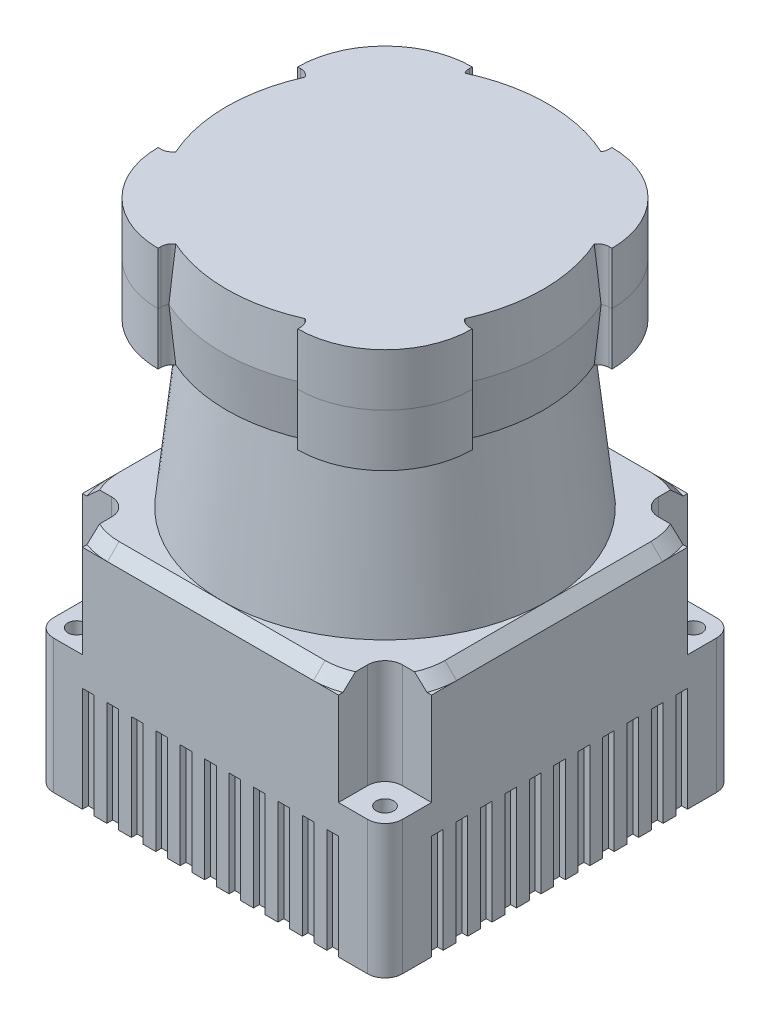
SolidWorks part; units mm, degrees
note: The reader was unsure of these and kept them because the rebuilt part matched: shared geometry of "Sketch11<3>".
ref_plane "Front Plane" through (0, 0, 0) normal (0, 0, 1) x (1, 0, 0)
ref_plane "Top Plane" through (0, 0, 0) normal (0, 1, 0) x (1, 0, 0)
ref_plane "Right Plane" through (0, 0, 0) normal (1, 0, 0) x (0, 0, -1)
sketch "Sketch2" plane through (0, 0, 0) normal (0, 0, 1) x (1, 0, 0)
  line L0 (0, 0) -> (-28, 0)
  line L1 (-28, 0) -> (-25, 28)
  line L2 (-25, 28) -> (0, 28)
  line L3 (0, 28) -> (0, 0)
  dimension "D1" = 28
  dimension "D2" = 25
  dimension "D3" = 28
revolve "Revolve1" add sketch "Sketch2" angle 360 about L3
sketch "Sketch3" plane through (0, 0, 0) normal (1, 0, 0) x (0, 0, -1)
  line L0 (25, 28) -> (-25, 28) construction
  line L1 (0, 28) -> (28, 28)
  line L2 (0, 28) -> (0, 0)
  line L3 (0, 0) -> (28, 0)
  line L4 (28, 28) -> (28, 0)
extrude "Boss-Extrude1" add sketch "Sketch3" along normal mid plane 10
sketch "Sketch4" plane through (0, 0, 0) normal (0, 1, 0) x (1, 0, 0)
  line L0 (-26.5, 30) -> (-26.5, 26.5) construction
  line L1 (27, -30) -> (-27, -30)
  line L2 (30, -27) -> (30, 27)
  line L3 (27, 30) -> (-27, 30)
  line L4 (-30, -27) -> (-30, 27)
  line L5 (30, -30) -> (-30, 30) construction
  line L6 (30, 30) -> (-30, -30) construction
  line L7 (-26.5, 26.5) -> (-30, 26.5) construction
  line L8 (26.5, 26.5) -> (26.5, 30) construction
  line L9 (30, 26.5) -> (26.5, 26.5) construction
  line L10 (26.5, -26.5) -> (30, -26.5) construction
  line L11 (26.5, -30) -> (26.5, -26.5) construction
  line L12 (-26.5, -26.5) -> (-26.5, -30) construction
  line L13 (-30, -26.5) -> (-26.5, -26.5) construction
  arc A0 (-27, -30) -> (-30, -27) centre (-27, -27) cw
  arc A1 (30, -27) -> (27, -30) centre (27, -27) cw
  arc A2 (30, 27) -> (27, 30) centre (27, 27) ccw
  arc A3 (-27, 30) -> (-30, 27) centre (-27, 27) ccw
  circle A4 centre (-26.5, 26.5) radius 1.5
  circle A5 centre (26.5, 26.5) radius 1.5
  circle A6 centre (26.5, -26.5) radius 1.5
  circle A7 centre (-26.5, -26.5) radius 1.5
  point P0 (0, 0)
  point P37 (0, 0)
  dimension "D2" = 3
  dimension "D4" = 3
  dimension "D1" = 60
  dimension "D3" = 3.5
  dimension "D5" = 4
extrude "Boss-Extrude2" add sketch "Sketch4" against normal blind 39 from offset 2 offset against normal yes
sketch "Sketch5" plane through (0, 0, 0) normal (0, 0, 1) x (1, 0, 0)
  line L0 (0, -2) -> (0, -41) construction
  line L1 (-27, -2) -> (27, -2) construction
  line L2 (-27, -41) -> (27, -41) construction
  circle A0 centre (-15, -32) radius 3.5
  circle A1 centre (15, -32) radius 3.5
  dimension "D3" = 7
  dimension "D1" = 9
  dimension "D2" = 15
extrude "Cut-Extrude1" cut sketch "Sketch5" along normal blind 5 from surface at -30 starting at face at (0, -21.5, -30)
sketch "Sketch7" plane through (0, -2, 0) normal (0, 1, 0) x (1, 0, 0)
  line L2 (27, 25) -> (-27, 25)
  line L3 (17.7, 25) -> (-17.7, 25)
  line L17 (-25, 27) -> (-25, -27)
  line L18 (-25, 17.7) -> (-25, -17.7)
  line L20 (-27, -25) -> (27, -25)
  line L21 (-17.7, -25) -> (17.7, -25)
  line L23 (25, -27) -> (25, 27)
  line L24 (25, -17.7) -> (25, 17.7)
  arc A0 (-17.7, 25) -> (-25, 17.7) centre (-17.7, 17.7) ccw
  arc A1 (-17.7, -25) -> (-25, -17.7) centre (-17.7, -17.7) cw
  arc A2 (25, -17.7) -> (17.7, -25) centre (17.7, -17.7) cw
  arc A3 (25, 17.7) -> (17.7, 25) centre (17.7, 17.7) ccw
  dimension "D5" = 7.3
  dimension "D6" = 7.3
  dimension "D1" = 5
  dimension "D2" = 5
  dimension "D3" = 5
  dimension "D4" = 5
sketch "Sketch9" plane through (0, 0, 0) normal (1, 0, 0) x (0, 0, -1)
  line L0 (-30, -2) -> (-28, 0)
  line L1 (-28, 0) -> (27.55, 0) construction
  line L2 (-28, 0) -> (-20, 0)
  line L3 (-20, 0) -> (-20, -2)
  line L4 (-27, -2) -> (27, -2) construction
  line L5 (-20, -2) -> (-30, -2)
  dimension "D1" = 10
sweep "Sweep2" add profiles "Sketch9" path "Sketch7"
sketch "Sketch6" plane through (0, 0, 0) normal (0, 1, 0) x (1, 0, 0)
  line L0 (-30, 22) -> (-25, 22)
  line L1 (-22, 25) -> (-22, 30)
  line L2 (27, 30) -> (17.7, 30) construction
  line L3 (-30, 27) -> (-30, 17.7) construction
  line L4 (-17.7, 30) -> (-27, 30) construction
  line L5 (-30, 27) -> (-30, 22)
  line L6 (30, 22) -> (30, 27)
  line L7 (25, 22) -> (30, 22)
  line L8 (22, 30) -> (22, 25)
  line L9 (27, 30) -> (22, 30)
  line L10 (22, -30) -> (27, -30)
  line L11 (22, -25) -> (22, -30)
  line L12 (30, -22) -> (25, -22)
  line L13 (30, -27) -> (30, -22)
  line L14 (-30, -22) -> (-30, -27)
  line L15 (-25, -22) -> (-30, -22)
  line L16 (-22, -30) -> (-22, -25)
  line L17 (-27, -30) -> (-22, -30)
  line L18 (-22, 30) -> (-27, 30)
  arc A0 (-22, 25) -> (-25, 22) centre (-25, 25) cw
  arc A2 (-27, 30) -> (-30, 27) centre (-27, 27) ccw construction
  arc A3 (30, 27) -> (27, 30) centre (27, 27) ccw
  arc A4 (25, 22) -> (22, 25) centre (25, 25) cw
  arc A5 (27, -30) -> (30, -27) centre (27, -27) ccw
  arc A6 (22, -25) -> (25, -22) centre (25, -25) cw
  arc A7 (-30, -27) -> (-27, -30) centre (-27, -27) ccw
  arc A8 (-25, -22) -> (-22, -25) centre (-25, -25) cw
  arc A9 (-27, 30) -> (-30, 27) centre (-27, 27) ccw
  point P9 (-22, 22)
  point P38 (0, 0)
  dimension "D2" = 3
  dimension "D1" = 8
  dimension "D3" = 4
extrude "Cut-Extrude2" cut sketch "Sketch6" against normal blind 18
sketch "Sketch10" plane through (0, -41, 0) normal (0, -1, 0) x (1, 0, 0)
  line L0 (-30, 0) -> (30, 0) construction
  line L1 (-30, -27) -> (-30, 27) construction
  line L2 (30, 27) -> (30, -27) construction
  line L3 (0, 30) -> (0, -30) construction
  line L4 (-27, 30) -> (27, 30) construction
  line L5 (27, -30) -> (-27, -30) construction
  line L6 (-30, 17.8) -> (-30, 15.8)
  line L7 (-30, 22) -> (-29, 22)
  line L8 (-30, 22) -> (-30, 20)
  line L9 (-30, 20) -> (-29, 20)
  line L10 (-29, 22) -> (-29, 20)
  line L11 (-30, 15.8) -> (-29, 15.8)
  line L12 (-29, 17.8) -> (-29, 15.8)
  line L13 (-30, 17.8) -> (-29, 17.8)
  line L14 (-30, 13.6) -> (-30, 11.6)
  line L15 (-30, 11.6) -> (-29, 11.6)
  line L16 (-29, 13.6) -> (-29, 11.6)
  line L17 (-30, 13.6) -> (-29, 13.6)
  line L18 (-30, 9.4) -> (-30, 7.4)
  line L19 (-30, 7.4) -> (-29, 7.4)
  line L20 (-29, 9.4) -> (-29, 7.4)
  line L21 (-30, 9.4) -> (-29, 9.4)
  line L22 (-30, 5.2) -> (-30, 3.2)
  line L23 (-30, 3.2) -> (-29, 3.2)
  line L24 (-29, 5.2) -> (-29, 3.2)
  line L25 (-30, 5.2) -> (-29, 5.2)
  line L26 (-30, 1) -> (-30, -1)
  line L27 (-30, -1) -> (-29, -1)
  line L28 (-29, 1) -> (-29, -1)
  line L29 (-30, 1) -> (-29, 1)
  line L30 (-30, -3.2) -> (-30, -5.2)
  line L31 (-30, -5.2) -> (-29, -5.2)
  line L32 (-29, -3.2) -> (-29, -5.2)
  line L33 (-30, -3.2) -> (-29, -3.2)
  line L34 (-30, -7.4) -> (-30, -9.4)
  line L35 (-30, -9.4) -> (-29, -9.4)
  line L36 (-29, -7.4) -> (-29, -9.4)
  line L37 (-30, -7.4) -> (-29, -7.4)
  line L38 (-30, -11.6) -> (-30, -13.6)
  line L39 (-30, -13.6) -> (-29, -13.6)
  line L40 (-29, -11.6) -> (-29, -13.6)
  line L41 (-30, -11.6) -> (-29, -11.6)
  line L42 (-30, -15.8) -> (-30, -17.8)
  line L43 (-30, -17.8) -> (-29, -17.8)
  line L44 (-29, -15.8) -> (-29, -17.8)
  line L45 (-30, -15.8) -> (-29, -15.8)
  line L46 (-30, -20) -> (-30, -22)
  line L47 (-30, -22) -> (-29, -22)
  line L48 (-29, -20) -> (-29, -22)
  line L49 (-30, -20) -> (-29, -20)
  line L50 (17.8, 30) -> (15.8, 30)
  line L51 (22, 30) -> (22, 29)
  line L52 (22, 30) -> (20, 30)
  line L53 (20, 30) -> (20, 29)
  line L54 (22, 29) -> (20, 29)
  line L55 (15.8, 30) -> (15.8, 29)
  line L56 (17.8, 29) -> (15.8, 29)
  line L57 (17.8, 30) -> (17.8, 29)
  line L58 (13.6, 30) -> (11.6, 30)
  line L59 (11.6, 30) -> (11.6, 29)
  line L60 (13.6, 29) -> (11.6, 29)
  line L61 (13.6, 30) -> (13.6, 29)
  line L62 (9.4, 30) -> (7.4, 30)
  line L63 (7.4, 30) -> (7.4, 29)
  line L64 (9.4, 29) -> (7.4, 29)
  line L65 (9.4, 30) -> (9.4, 29)
  line L66 (5.2, 30) -> (3.2, 30)
  line L67 (3.2, 30) -> (3.2, 29)
  line L68 (5.2, 29) -> (3.2, 29)
  line L69 (5.2, 30) -> (5.2, 29)
  line L70 (1, 30) -> (-1, 30)
  line L71 (-1, 30) -> (-1, 29)
  line L72 (1, 29) -> (-1, 29)
  line L73 (1, 30) -> (1, 29)
  line L74 (-3.2, 30) -> (-5.2, 30)
  line L75 (-5.2, 30) -> (-5.2, 29)
  line L76 (-3.2, 29) -> (-5.2, 29)
  line L77 (-3.2, 30) -> (-3.2, 29)
  line L78 (-7.4, 30) -> (-9.4, 30)
  line L79 (-9.4, 30) -> (-9.4, 29)
  line L80 (-7.4, 29) -> (-9.4, 29)
  line L81 (-7.4, 30) -> (-7.4, 29)
  line L82 (-11.6, 30) -> (-13.6, 30)
  line L83 (-13.6, 30) -> (-13.6, 29)
  line L84 (-11.6, 29) -> (-13.6, 29)
  line L85 (-11.6, 30) -> (-11.6, 29)
  line L86 (-15.8, 30) -> (-17.8, 30)
  line L87 (-17.8, 30) -> (-17.8, 29)
  line L88 (-15.8, 29) -> (-17.8, 29)
  line L89 (-15.8, 30) -> (-15.8, 29)
  line L90 (-20, 30) -> (-22, 30)
  line L91 (-22, 30) -> (-22, 29)
  line L92 (-20, 29) -> (-22, 29)
  line L93 (-20, 30) -> (-20, 29)
  line L94 (30, -17.8) -> (30, -15.8)
  line L95 (30, -22) -> (29, -22)
  line L96 (30, -22) -> (30, -20)
  line L97 (30, -20) -> (29, -20)
  line L98 (29, -22) -> (29, -20)
  line L99 (30, -15.8) -> (29, -15.8)
  line L100 (29, -17.8) -> (29, -15.8)
  line L101 (30, -17.8) -> (29, -17.8)
  line L102 (30, -13.6) -> (30, -11.6)
  line L103 (30, -11.6) -> (29, -11.6)
  line L104 (29, -13.6) -> (29, -11.6)
  line L105 (30, -13.6) -> (29, -13.6)
  line L106 (30, -9.4) -> (30, -7.4)
  line L107 (30, -7.4) -> (29, -7.4)
  line L108 (29, -9.4) -> (29, -7.4)
  line L109 (30, -9.4) -> (29, -9.4)
  line L110 (30, -5.2) -> (30, -3.2)
  line L111 (30, -3.2) -> (29, -3.2)
  line L112 (29, -5.2) -> (29, -3.2)
  line L113 (30, -5.2) -> (29, -5.2)
  line L114 (30, -1) -> (30, 1)
  line L115 (30, 1) -> (29, 1)
  line L116 (29, -1) -> (29, 1)
  line L117 (30, -1) -> (29, -1)
  line L118 (30, 3.2) -> (30, 5.2)
  line L119 (30, 5.2) -> (29, 5.2)
  line L120 (29, 3.2) -> (29, 5.2)
  line L121 (30, 3.2) -> (29, 3.2)
  line L122 (30, 7.4) -> (30, 9.4)
  line L123 (30, 9.4) -> (29, 9.4)
  line L124 (29, 7.4) -> (29, 9.4)
  line L125 (30, 7.4) -> (29, 7.4)
  line L126 (30, 11.6) -> (30, 13.6)
  line L127 (30, 13.6) -> (29, 13.6)
  line L128 (29, 11.6) -> (29, 13.6)
  line L129 (30, 11.6) -> (29, 11.6)
  line L130 (30, 15.8) -> (30, 17.8)
  line L131 (30, 17.8) -> (29, 17.8)
  line L132 (29, 15.8) -> (29, 17.8)
  line L133 (30, 15.8) -> (29, 15.8)
  line L134 (30, 20) -> (30, 22)
  line L135 (30, 22) -> (29, 22)
  line L136 (29, 20) -> (29, 22)
  line L137 (30, 20) -> (29, 20)
  line L138 (-17.8, -30) -> (-15.8, -30)
  line L139 (-22, -30) -> (-22, -29)
  line L140 (-22, -30) -> (-20, -30)
  line L141 (-20, -30) -> (-20, -29)
  line L142 (-22, -29) -> (-20, -29)
  line L143 (-15.8, -30) -> (-15.8, -29)
  line L144 (-17.8, -29) -> (-15.8, -29)
  line L145 (-17.8, -30) -> (-17.8, -29)
  line L146 (-13.6, -30) -> (-11.6, -30)
  line L147 (-11.6, -30) -> (-11.6, -29)
  line L148 (-13.6, -29) -> (-11.6, -29)
  line L149 (-13.6, -30) -> (-13.6, -29)
  line L150 (-9.4, -30) -> (-7.4, -30)
  line L151 (-7.4, -30) -> (-7.4, -29)
  line L152 (-9.4, -29) -> (-7.4, -29)
  line L153 (-9.4, -30) -> (-9.4, -29)
  line L154 (-5.2, -30) -> (-3.2, -30)
  line L155 (-3.2, -30) -> (-3.2, -29)
  line L156 (-5.2, -29) -> (-3.2, -29)
  line L157 (-5.2, -30) -> (-5.2, -29)
  line L158 (-1, -30) -> (1, -30)
  line L159 (1, -30) -> (1, -29)
  line L160 (-1, -29) -> (1, -29)
  line L161 (-1, -30) -> (-1, -29)
  line L162 (3.2, -30) -> (5.2, -30)
  line L163 (5.2, -30) -> (5.2, -29)
  line L164 (3.2, -29) -> (5.2, -29)
  line L165 (3.2, -30) -> (3.2, -29)
  line L166 (7.4, -30) -> (9.4, -30)
  line L167 (9.4, -30) -> (9.4, -29)
  line L168 (7.4, -29) -> (9.4, -29)
  line L169 (7.4, -30) -> (7.4, -29)
  line L170 (11.6, -30) -> (13.6, -30)
  line L171 (13.6, -30) -> (13.6, -29)
  line L172 (11.6, -29) -> (13.6, -29)
  line L173 (11.6, -30) -> (11.6, -29)
  line L174 (15.8, -30) -> (17.8, -30)
  line L175 (17.8, -30) -> (17.8, -29)
  line L176 (15.8, -29) -> (17.8, -29)
  line L177 (15.8, -30) -> (15.8, -29)
  line L178 (20, -30) -> (22, -30)
  line L179 (22, -30) -> (22, -29)
  line L180 (20, -29) -> (22, -29)
  line L181 (20, -30) -> (20, -29)
  point P192 (0, 0)
  dimension "D1" = 1
  dimension "D2" = 2
  dimension "D3" = 8
  dimension "D5" = 4
  dimension "D4" = 11
extrude "Cut-Extrude3" cut sketch "Sketch10" against normal blind 18
ref_plane "Plane1" through (0, 37, 0) normal (0, 1, 0) x (1, 0, 0)
sketch "Sketch11" plane through (0, 37, 0) normal (0, 1, 0) x (1, 0, 0)
  line L0 (-10, 24.5) -> (10, 24.5)
  line L1 (27, -27) -> (-27, -27) construction
  line L2 (27, -27) -> (27, 27) construction
  line L3 (27, 27) -> (-27, 27) construction
  line L4 (-27, -27) -> (-27, 7.2357) construction
  line L5 (27, -27) -> (-27, 27) construction
  line L6 (27, 27) -> (-27, -27) construction
  line L7 (0, 28) -> (0, 24.5) construction
  line L8 (-12, 26.5) -> (-12, 27)
  line L9 (12, 26.5) -> (12, 27)
  line L10 (26.5, 12) -> (27, 12)
  line L11 (24.5, 10) -> (24.5, -10)
  line L12 (26.5, -12) -> (27, -12)
  line L13 (12, -26.5) -> (12, -27)
  line L14 (10, -24.5) -> (-10, -24.5)
  line L15 (-12, -26.5) -> (-12, -27)
  line L16 (-26.5, -12) -> (-27, -12)
  line L17 (-24.5, -10) -> (-24.5, 10)
  line L18 (-26.5, 12) -> (-27, 12)
  circle A0 centre (0, 0) radius 28
  arc A1 (-12, 27) -> (-27, 12) centre (-12, 12) ccw
  arc A2 (26.5, 12) -> (24.5, 10) centre (26.5, 10) ccw
  arc A3 (-27, -12) -> (-12, -27) centre (-12, -12) ccw
  arc A4 (12, 26.5) -> (10, 24.5) centre (10, 26.5) cw
  arc A5 (26.5, -12) -> (24.5, -10) centre (26.5, -10) cw
  arc A7 (12, -27) -> (27, -12) centre (12, -12) ccw
  arc A8 (-12, 26.5) -> (-10, 24.5) centre (-10, 26.5) ccw
  arc A9 (12, -26.5) -> (10, -24.5) centre (10, -26.5) ccw
  arc A10 (-12, -26.5) -> (-10, -24.5) centre (-10, -26.5) cw
  arc A11 (-26.5, -12) -> (-24.5, -10) centre (-26.5, -10) ccw
  arc A12 (-26.5, 12) -> (-24.5, 10) centre (-26.5, 10) cw
  arc A13 (27, 12) -> (12, 27) centre (12, 12) ccw
  point P0 (0, 0)
  point P20 (0, 24.5)
  point P27 (12, 24.5)
  point P30 (-12, 24.5)
  point P55 (0, 0)
  dimension "D2" = 56
  dimension "D4" = 24
  dimension "D6" = 2
  dimension "D1" = 54
  dimension "D5" = 3.5
extrude "Boss-Extrude3" add sketch "Sketch11" along normal mid plane 18 draft 5
extrude "Boss-Extrude4" add sketch "Sketch11<3>" along normal mid plane 18 contours L18 A12 A0 A8 L8 A1 | A0 A12 L17 A11 A10 L14 A9 A5 L11 A2 A4 L0 A8 | A11 L16 A3 L15 A10 A0 | A9 L13 A7 L12 A5 A0 | L10 A13 L9 A4 A0 A2 | A0 A8 L0 A4
sketch "Sketch11<3>" plane through (0, 37, 0) normal (0, 1, 0) x (1, 0, 0) same geometry as "Sketch11"
split "Split1" trim tools "Plane1" bodies to split 110 resulting bodies 111 112
